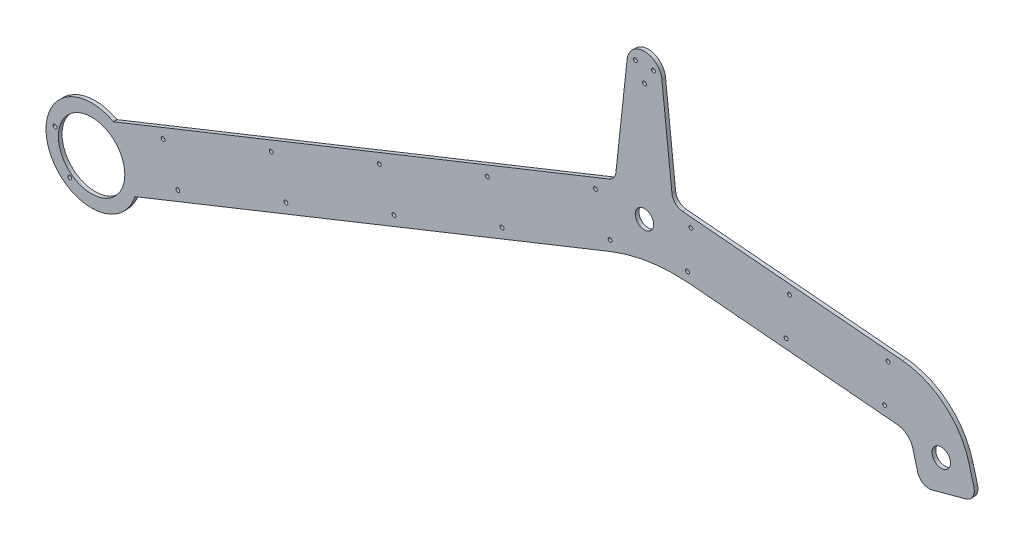
SolidWorks part; units mm, degrees
ref_plane "Front Plane" through (0, 0, 0) normal (0, 0, 1) x (1, 0, 0)
ref_plane "Top Plane" through (0, 0, 0) normal (0, 1, 0) x (1, 0, 0)
ref_plane "Right Plane" through (0, 0, 0) normal (1, 0, 0) x (0, 0, -1)
sketch "Sketch1" plane through (0, 0, 0) normal (0, 0, 1) x (1, 0, 0)
  line L0 (-325, 0) -> (325, 0) construction
  line L1 (-475, -190) -> (-325, 0) construction
  line L2 (325, 0) -> (475, -190) construction
  line L3 (-75, -190) -> (145, -190) construction
  line L4 (145, -190) -> (365, -190) construction
  line L5 (-25.1427, 16.8688) -> (-516.7815, -179.7868)
  line L6 (-516.7815, -179.7868) -> (-498.2119, -226.2106)
  line L7 (-498.2119, -226.2106) -> (-29.4264, -38.6964)
  line L8 (-507.4967, -202.9987) -> (-475, -190) construction
  line L9 (39.3556, -28.5387) -> (217.3643, -44.1124)
  line L11 (221.7221, 5.6973) -> (24.4857, 22.9533)
  line L12 (-25.1427, 16.8688) -> (-6.5731, -29.5551) construction
  line L13 (35, -190) -> (255, -49.8445) construction
  line L14 (255, -49.8445) -> (475, -190) construction
  line L15 (-25.1427, 16.8688) -> (-14.9133, 111.6102)
  line L16 (14.9133, 111.6102) -> (24.4857, 22.9533)
  line L17 (325, 0) -> (325, 80) construction
  line L18 (325, 80) -> (-325, 80) construction
  line L19 (-325, 80) -> (-325, 0) construction
  line L20 (24.4857, 22.9533) -> (20.1279, -26.8565) construction
  line L21 (-15.8579, -6.3432) -> (0, 0) construction
  line L22 (-25.1427, 16.8688) -> (24.4857, 22.9533) construction
  line L23 (230.5459, -55.173) -> (237.3223, -80.4632)
  line L24 (237.3223, -80.4632) -> (285.6186, -67.5222)
  line L25 (285.6186, -67.5222) -> (278.8422, -42.2321)
  line L26 (261.4705, -73.9927) -> (255, -49.8445) construction
  line L29 (0, 0) -> (22.3068, -1.9516) construction
  circle A0 centre (0, 0) radius 7.9375
  circle A1 centre (-475, -190) radius 110 construction
  circle A2 centre (35, -190) radius 110 construction
  circle A3 centre (475, -190) radius 110 construction
  circle A5 centre (255, -49.8445) radius 7.9375
  arc A6 (-14.9133, 111.6102) -> (14.9133, 111.6102) centre (0, 110) cw
  arc A7 (217.3643, -44.1124) -> (230.5459, -55.173) centre (216.057, -59.0553) cw
  arc A8 (221.7221, 5.6973) -> (278.8422, -42.2321) centre (216.057, -59.0553) cw
  arc A9 (-29.4264, -38.6964) -> (39.3556, -28.5387) centre (26.2822, -177.9679) cw
  point P11 (-475, -300)
  dimension "D1" = 15.875
  dimension "D4" = 220
  dimension "D12" = 30
  dimension "D16" = 15
  dimension "D17" = 150
  dimension "D2" = 325
  dimension "D3" = 650
  dimension "D6" = 150
  dimension "D7" = 50
  dimension "D8" = 35
  dimension "D10" = 80
  dimension "D11" = 30
  dimension "D13" = 25
  dimension "D9" = 115
  dimension "D14" = 5
  dimension "D15" = 75
  dimension "D5" = 380
extrude "Base" add sketch "Sketch1" along normal blind 3.175
fillet "Fillet1" radius 10 6 edges at (24.4857, 22.9533, 1.5875) (-25.1427, 16.8688, 1.5875) (237.3223, -80.4632, 1.5875) (285.6186, -67.5222, 1.5875) (-498.2119, -226.2106, 1.5875) (-516.7815, -179.7868, 1.5875)
sketch "Sketch2" plane through (0, 0, 3.175) normal (0, 0, 1) x (1, 0, 0)
  circle A0 centre (0, 110) radius 9 construction
  circle A1 centre (-7.7942, 114.5) radius 1.65
  circle A2 centre (7.7942, 114.5) radius 1.65
  circle A3 centre (0, 101) radius 1.65
  point P11 (0, 110)
  dimension "D2" = 3.3
  dimension "D3" = 18
  dimension "D1" = 3
extrude "Differential Attachment" cut sketch "Sketch2" against normal through all
sketch "Sketch3" plane through (0, 0, 3.175) normal (0, 0, 1) x (1, 0, 0)
  line L0 (-492.6411, -213.2119) -> (-496.5803, -222.4034) construction
  line L1 (-503.7828, -185.3576) -> (-512.9742, -181.4184) construction
  line L3 (-490.7841, -223.2395) -> (-493.7552, -215.8117) construction
  line L4 (-488.9272, -222.4967) -> (-29.4264, -38.6964) construction
  line L5 (-509.3536, -176.8156) -> (-506.3825, -184.2434) construction
  line L6 (-30.7255, 14.6356) -> (-507.4967, -176.0728) construction
  line L7 (-29.5169, -30.1163) -> (-42.1442, 1.4519) construction
  line L8 (-35.8305, -14.3322) -> (0, 0) construction
  line L9 (0, 0) -> (38.4438, -3.3634) construction
  line L10 (221.7221, 5.6973) -> (32.674, 22.2369) construction
  line L11 (39.9255, 13.5719) -> (36.9622, -20.2987) construction
  circle A0 centre (-506.3825, -184.2434) radius 1.65
  circle A1 centre (-493.7552, -215.8117) radius 1.65
  arc A3 (-501.9258, -216.9258) -> (-488.9272, -222.4967) centre (-492.6411, -213.2119) ccw construction
  arc A4 (-507.4967, -176.0728) -> (-513.0675, -189.0715) centre (-503.7828, -185.3576) ccw construction
  circle A5 centre (-400.9076, -178.6726) radius 1.65
  circle A6 centre (-413.5348, -147.1044) radius 1.65
  circle A7 centre (-308.0599, -141.5335) radius 1.65
  circle A8 centre (-320.6872, -109.9653) radius 1.65
  circle A9 centre (-215.2122, -104.3944) radius 1.65
  circle A10 centre (-227.8395, -72.8262) radius 1.65
  circle A11 centre (-122.3646, -67.2554) radius 1.65
  circle A12 centre (-134.9918, -35.6872) radius 1.65
  circle A13 centre (-29.5169, -30.1163) radius 1.65
  circle A14 centre (-42.1442, 1.4519) radius 1.65
  circle A15 centre (39.9255, 13.5719) radius 1.65
  circle A16 centre (36.9622, -20.2987) radius 1.65
  circle A17 centre (124.602, 6.1637) radius 1.65
  circle A18 centre (121.6387, -27.7069) radius 1.65
  circle A19 centre (209.2786, -1.2446) radius 1.65
  circle A20 centre (206.3153, -35.1152) radius 1.65
  point P53 (38.4438, -3.3634)
  dimension "D2" = 3.3
  dimension "D1" = 8
  dimension "D5" = 100
  dimension "D6" = 85
  dimension "D3" = 6
  dimension "D4" = 3
extrude "Strut Holes" cut sketch "Sketch3" against normal through all
sketch "Sketch4" plane through (0, 0, 3.175) normal (0, 0, 1) x (1, 0, 0)
  line L2 (-495.6808, -181.1368) -> (-466.1368, -169.3192) construction
  line L3 (-30.7255, 14.6356) -> (-507.4967, -176.0728) construction
  circle A0 centre (-475, -190) radius 16.05
  circle A1 centre (-475, -190) radius 22.5 construction
  circle A2 centre (-466.1368, -169.3192) radius 2.75
  circle A3 centre (-454.3192, -198.8632) radius 2.75
  circle A4 centre (-483.8632, -210.6808) radius 2.75
  circle A5 centre (-495.6808, -181.1368) radius 2.75
  point P17 (-475, -190)
  dimension "D1" = 32.1
  dimension "D2" = 45
  dimension "D4" = 5.5
  dimension "D3" = 4
extrude "Motor Connection" [suppressed] cut sketch "Sketch4" against normal through all
sketch "Sketch5" plane through (0, 0, 3.175) normal (0, 0, 1) x (1, 0, 0)
  circle A0 centre (-475, -190) radius 28.55
  circle A1 centre (-475, -190) radius 39.1548
  arc A3 (-507.4967, -176.0728) -> (-513.0675, -189.0715) centre (-503.7828, -185.3576) ccw construction
  circle A4 centre (-506.3825, -184.2434) radius 1.65 construction
  circle A5 centre (-493.7552, -215.8117) radius 1.65 construction
  circle A6 centre (-506.3825, -184.2434) radius 1.65
  circle A7 centre (-493.7552, -215.8117) radius 1.65
  line M34 (-30.7255, 14.6356) -> (-507.4967, -176.0728)
  line M38 (-488.9272, -222.4967) -> (-29.4264, -38.6964)
  dimension "D1" = 57.1
extrude "Motor Ring" add sketch "Sketch5" against normal up to surface (3.175 mm away) up to face at (-504.7325, -184.2434, 0)
extrude "Motor Slot" cut sketch "Sketch5<3>" against normal blind 6.5 contours A0 M34 M38 region at (-475, -190, 3.175)
sketch "Sketch5<3>" plane through (0, 0, 3.175) normal (0, 0, 1) x (1, 0, 0) same geometry as "Sketch5"
equation "\"D3@Sketch1\"= \"Chassis Length@Rocker Bogie Assy.Assembly\""
equation "\"D10@Sketch1\"= \"Chassis Height@Rocker Bogie Assy.Assembly\" / 2"
equation "\"D2@Sketch1\"= \"Front to Pivot@Rocker Bogie Assy.Assembly\""
equation "\"D6@Sketch1\"= \"Wheel to Frame@Rocker Bogie Assy.Assembly\""
equation "\"D9@Sketch1\"=\"Bogie Angle@Rocker Bogie Assy.Assembly\""
equation "\"D5@Sketch1\"=\"Chassis Top to Ground@Rocker Bogie Assy.Assembly\""
equation "\"D4@Sketch1\"=\"Wheel Diameter@Rocker Bogie Assy.Assembly\""
equation "\"D7@Sketch1\"=\"Leg Width@Rocker Bogie Assy.Assembly\""
equation "\"D1@Base\"=\"Plate Thickness@Rocker Bogie Assy.Assembly\""
